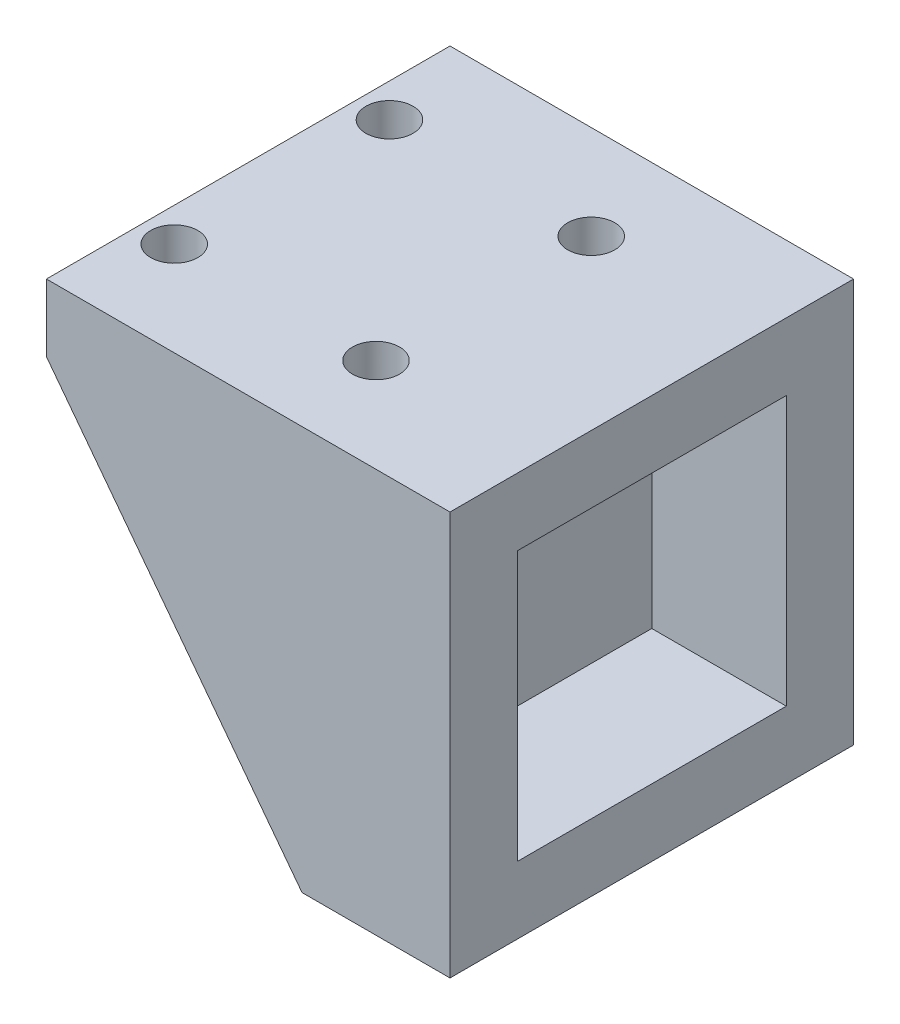
SolidWorks part; units mm, degrees
material "ABS"
ref_plane "Front Plane" through (0, 0, 0) normal (0, 0, 1) x (1, 0, 0)
ref_plane "Top Plane" through (0, 0, 0) normal (0, 1, 0) x (1, 0, 0)
ref_plane "Right Plane" through (0, 0, 0) normal (1, 0, 0) x (0, 0, -1)
sketch "Sketch1" plane through (0, 0, 0) normal (0, 1, 0) x (1, 0, 0)
  line L1 (0, 0) -> (30, 0)
  line L2 (0, 0) -> (0, 30)
  line L3 (0, 30) -> (30, 30)
  line L4 (30, 0) -> (30, 30)
  circle A0 centre (2.5, 7) radius 1.75
  circle A1 centre (17.5, 7) radius 1.75
  circle A2 centre (2.5, 23) radius 1.75
  circle A3 centre (17.5, 23) radius 1.75
  dimension "D4" = 3.5
  dimension "D5" = 3.5
  dimension "D8" = 3.5
  dimension "D10" = 3.5
  dimension "D1" = 30
  dimension "D2" = 30
  dimension "D3" = 15
  dimension "D6" = 2.5
  dimension "D7" = 7
  dimension "D9" = 16
extrude "Boss-Extrude1" add sketch "Sketch1" along normal blind 5
sketch "Sketch2" plane through (0, 0, 0) normal (0, -1, 0) x (1, 0, 0)
  line L0 (30, -30) -> (0, -30) construction
  line L1 (30, 0) -> (19, 0)
  line L2 (30, 0) -> (30, -30)
  line L3 (30, -30) -> (19, -30)
  line L4 (19, 0) -> (19, -30)
  dimension "D1" = 11
extrude "Boss-Extrude2" add sketch "Sketch2" along normal blind 25
sketch "Sketch3" plane through (30, 0, 0) normal (1, 0, 0) x (0, 0, -1)
  line L0 (30, 5) -> (30, -25) construction
  line L1 (25, -20) -> (5, -20)
  line L2 (25, -20) -> (25, 0)
  line L3 (25, 0) -> (5, 0)
  line L4 (5, -20) -> (5, 0)
  line L5 (30, -25) -> (0, -25) construction
  dimension "D1" = 20
  dimension "D2" = 20
  dimension "D3" = 5
  dimension "D4" = 5
extrude "Cut-Extrude1" cut sketch "Sketch3" against normal blind 10
sketch "Sketch8" plane through (0, 0, -30) normal (0, 0, -1) x (-1, 0, 0)
  line L1 (-19, -25) -> (-19, 0) construction
  line L3 (-19, 0) -> (0, 0) construction
  line L4 (-19, 0) -> (0, 0)
  line L5 (0, 0) -> (-19, -25)
  line L6 (-19, -25) -> (-19, 0)
extrude "Boss-Extrude3" add sketch "Sketch8" against normal blind 3
sketch "Sketch11" plane through (0, 0, 0) normal (0, 0, 1) x (1, 0, 0)
  line L0 (19, -25) -> (0, 0)
  line L1 (0, 0) -> (19, 0)
  line L2 (19, 0) -> (19, -25)
extrude "Boss-Extrude4" add sketch "Sketch11" against normal blind 3
sketch "Sketch12" plane through (0, 0, 0) normal (0, -1, 0) x (1, 0, 0)
  circle A0 centre (17.5, -23) radius 2.9
  circle A1 centre (17.5, -7) radius 2.9
  dimension "D1" = 5.8
  dimension "D2" = 5.8
extrude "Cut-Extrude3" cut sketch "Sketch12" against normal blind 2
chamfer "Chamfer3" distance 1 angle 75 6 edges at (19, 0, -23) (19, 0, -7) (19.563, 0, -20.9619) (19.563, 0, -25.0381) (19.563, 0, -4.9619) (19.563, 0, -9.0381)
delete or keep bodies "Body-Delete/Keep 1" [suppressed] type delete bodies bodies 134
